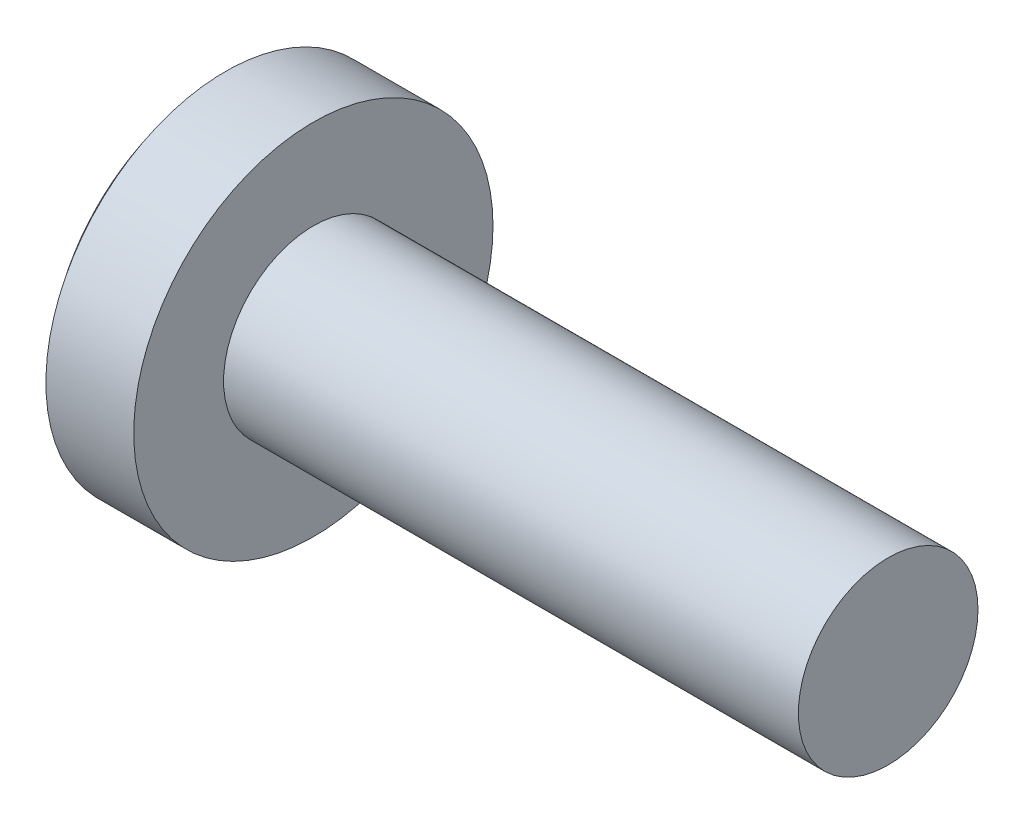
SolidWorks part; units mm, degrees
ref_plane "Front" through (0, 0, 0) normal (0, 0, 1) x (1, 0, 0)
ref_plane "Top" through (0, 0, 0) normal (0, 1, 0) x (1, 0, 0)
ref_plane "Right" through (0, 0, 0) normal (1, 0, 0) x (0, 0, -1)
sketch "Sketch1" plane through (0, 0, 0) normal (0, 0, 1) x (1, 0, 0)
  line L0 (10.1, 1.25) -> (3, 1.25)
  line L1 (2.1, 1.55) -> (2.1, 2.5)
  line L2 (2.1, 2.5) -> (0.8775, 2.5)
  line L3 (3, 1.25) -> (2.4, 1.25) construction
  line L4 (10.1, 1.25) -> (10.1, 0)
  line L5 (4.5158, 0) -> (-13.5157, 0) construction
  line L6 (10.1, 0) -> (0, 0)
  line L7 (3, 1.25) -> (2.1, 1.25)
  line L8 (2.1, 1.25) -> (2.1, 1.55)
  arc A0 (0.8775, 2.5) -> (0, 0) centre (4, 0) ccw
  arc A1 (2.1, 1.55) -> (2.4, 1.25) centre (2.4, 1.55) ccw construction
  dimension "r" = 0.3
  dimension "r1" = 4
  dimension "dk" = 5
  dimension "l" = 8
  dimension "k" = 2.1
  dimension "a" = 0.9
  dimension "da" = 3.1
revolve "Base" add sketch "Sketch1" angle 360 about L5
cosmetic thread "ThreadCosmetic1" [suppressed] parameters "bb"=12, "THD_MINOR"=2.013
sketch "Sketch6" plane through (0, 0, 0) normal (1, 0, 0) x (0, 0, -1)
  line L0 (-1.9271, 0) -> (2.0512, 0) construction
  line L1 (0, 1.8651) -> (0, -2.0207) construction
  line L2 (0.27, 0.27) -> (0.27, 1.35)
  line L3 (0.27, 1.35) -> (-0.27, 1.35)
  line L4 (-0.27, 0.27) -> (-0.27, 1.35)
  line L5 (0.27, 0.27) -> (1.35, 0.27)
  line L6 (1.35, 0.27) -> (1.35, -0.27)
  line L7 (-1.35, 0.27) -> (-1.35, -0.27)
  line L8 (-0.27, 0.27) -> (-1.35, 0.27)
  line L9 (-0.27, -0.27) -> (-1.35, -0.27)
  line L10 (0.27, -0.27) -> (1.35, -0.27)
  line L11 (-0.27, -0.27) -> (-0.27, -1.35)
  line L12 (0.27, -1.35) -> (-0.27, -1.35)
  line L13 (0.27, -0.27) -> (0.27, -1.35)
  point P16 (-1.35, 0)
  point P17 (1.35, 0)
extrude "CrossRecess" cut sketch "Sketch6" along normal blind 1.47
fillet "Fillet5" radius 0.3 4 edges at (0.7441, -0.27, 0.27) (0.7441, -0.27, -0.27) (0.7441, 0.27, 0.27) (0.7441, 0.27, -0.27)
draft "Draft1" type of draft neutral plane draft angle 30 neutral plane "Right" faces to draft 4 face at (0.8548, -1.35, 0) face at (0.8548, 0, -1.35) face at (0.8548, 0, 1.35) face at (0.8548, 1.35, 0) neutral plane through (0, 0, 0) neutral plane normal (1, 0, 0) reverse direction yes parameters "D1"=30
sketch "Sketch7" plane through (0, 0, 0) normal (1, 0, 0) x (0, 0, -1)
  line L0 (-2.0126, 0) -> (1.9757, 0) construction
  line L1 (0, 1.9314) -> (0, -2.0126) construction
  line L2 (0, 0) -> (1.5555, 1.5555) construction
  line L3 (0, 0.4035) -> (0.9546, 0.9546)
  line L4 (-1.5402, 1.5402) -> (0, 0) construction
  line L5 (0.4035, 0) -> (0.9546, 0.9546)
  line L6 (0, -0.4035) -> (0.9546, -0.9546)
  line L7 (0.4035, 0) -> (0.9546, -0.9546)
  line L8 (-0.4035, 0) -> (-0.9546, -0.9546)
  line L9 (0, -0.4035) -> (-0.9546, -0.9546)
  line L10 (-0.4035, 0) -> (-0.9546, 0.9546)
  line L11 (0, 0.4035) -> (-0.9546, 0.9546)
  dimension "D3" = 15
extrude "Cut-Extrude3" [suppressed] cut sketch "Sketch7" along normal blind 40.2 draft 9
sketch "Sketch8" plane through (0, 0, 0) normal (0, 0, 1) x (1, 0, 0)
  line L0 (-14.9, 1.25) -> (-16, 1.0065)
  line L1 (-16, 1.0065) -> (2.1, 1.0065)
  line L2 (10.1, -1.25) -> (10.1, 1.25) construction
  line L3 (2.1, -2.5) -> (2.1, 2.5) construction
  line L6 (2.1, 1.0065) -> (2.1, 2.5)
  line L7 (2.1, 2.5) -> (-14.9, 2.5)
  line L8 (-14.9, 2.5) -> (-14.9, 1.25)
  line L9 (73.4853, 0) -> (63.9694, 0) construction
  dimension "x" = 1.1
sketch "Sketch9" plane through (0, 0, 0) normal (0, 0, 1) x (1, 0, 0)
  line L0 (10.1, 1.0391) -> (10.2218, 1.25)
  line L1 (10.2218, 1.25) -> (10.2218, 1.4935)
  line L2 (10.2218, 1.4935) -> (9.9783, 1.4935)
  line L3 (9.9783, 1.4935) -> (9.9783, 1.25)
  line L4 (9.9783, 1.25) -> (10.1, 1.0391)
  line L5 (10.1, -1.25) -> (10.1, 1.25) construction
  line L6 (0, 0) -> (76.7811, 0) construction
  dimension "D1" = 2.5
  dimension "D2" = 0.2435
revolve "Cut-Revolve10" [suppressed] cut sketch "Sketch9" angle 360 about L6
pattern_linear "LPattern10" [suppressed] count 41 spacing 0.2922 along (-1, 0, 0) of bodies 105
equation "\"D1@Sketch6\" = \"m@Sketch6\" / 5"
equation "\"D1@CrossRecess\" = 0.7*\"k@Sketch1\""
equation "\"D1@Sketch9\" = \"d@Sketch1\" "
equation "\"D2@Sketch9\" =  ( \"d@Sketch1\" - \"THD_MINOR@ThreadCosmetic1\" )  / 2"
equation "\"D3@LPattern10\" =\"D2@Sketch9\" * 1.2"
equation "\"D1@LPattern10\" = \"bb@ThreadCosmetic1\" / \"D3@LPattern10\" "
